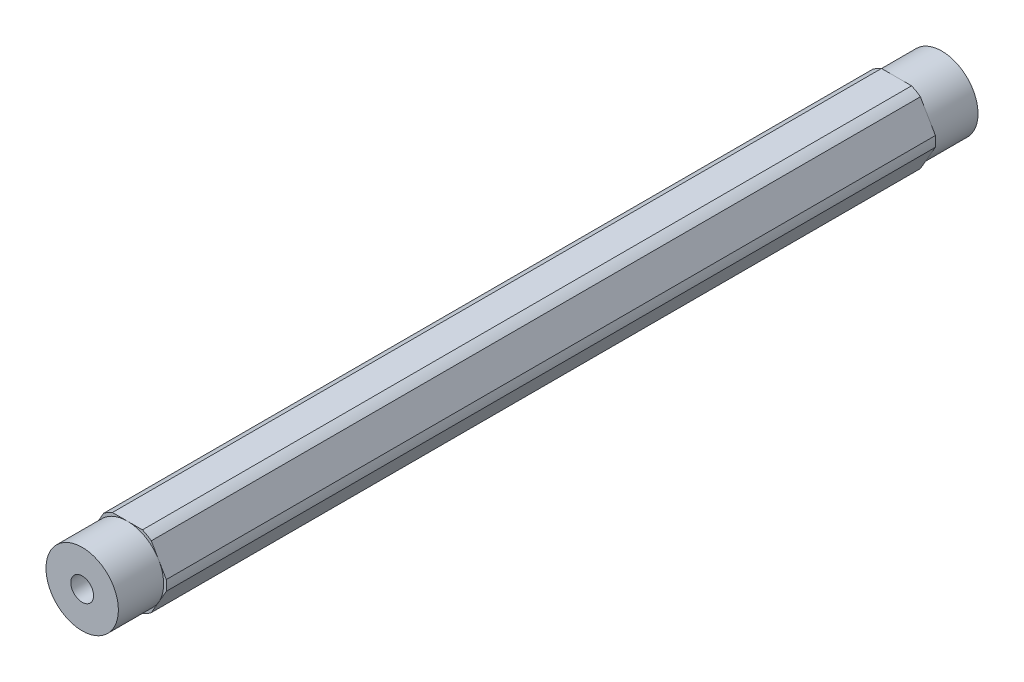
SolidWorks part; units mm, degrees
material "6061-T6 (SS)"
ref_plane "Front Plane" through (0, 0, 0) normal (0, 0, 1) x (1, 0, 0)
ref_plane "Top Plane" through (0, 0, 0) normal (0, 1, 0) x (1, 0, 0)
ref_plane "Right Plane" through (0, 0, 0) normal (1, 0, 0) x (0, 0, -1)
sketch "Sketch1" plane through (0, 0, 0) normal (0, 0, 1) x (1, 0, 0)
  line L1 (3.6662, 6.35) -> (-3.6662, 6.35)
  line L2 (-3.6662, 6.35) -> (-7.3323, 0)
  line L3 (-7.3323, 0) -> (-3.6662, -6.35)
  line L4 (-3.6662, -6.35) -> (3.6662, -6.35)
  line L5 (3.6662, -6.35) -> (7.3323, 0)
  line L6 (7.3323, 0) -> (3.6662, 6.35)
  circle A0 centre (0, 0) radius 6.35 construction
  circle A1 centre (0, 0) radius 2
  circle A2 centre (0, 0) radius 6.875
  point P1 (0, 6.35)
  dimension "D2" = 13.75
  dimension "D3" = 4
  dimension "D1" = 12.7
extrude "Boss-Extrude1" add sketch "Sketch1" along normal mid plane 134.8867 contours L6 A2 L1 L2 L3 L4 L5 A1 region at (3.3439, 5.7918, 0)
sketch "Sketch4" plane through (0, 0, 67.4433) normal (0, 0, 1) x (1, 0, 0)
  circle A0 centre (0, 0) radius 6.35
  circle A1 centre (0, 0) radius 2 construction
  circle A2 centre (0, 0) radius 2
  dimension "D1" = 12.7
extrude "Boss-Extrude2" add sketch "Sketch4" along normal blind 7.9375
mirror "Mirror1" about plane through (0, 0, 0) normal (0, 0, 1) of "Boss-Extrude2"
equation "\"D2@Sketch1\"=13.75mm"
equation "\"D3@Sketch1\"=4mm"
